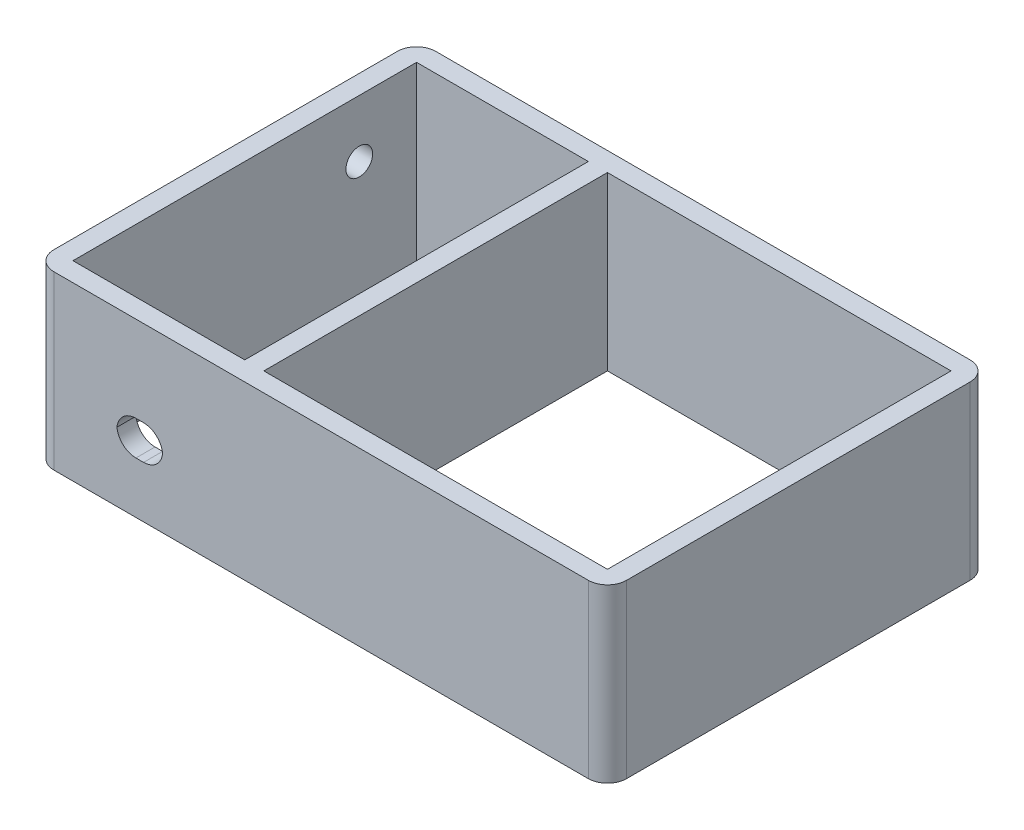
SolidWorks part; units mm, degrees
ref_plane "Front Plane" through (0, 0, 0) normal (0, 0, 1) x (1, 0, 0)
ref_plane "Top Plane" through (0, 0, 0) normal (0, 1, 0) x (1, 0, 0)
ref_plane "Right Plane" through (0, 0, 0) normal (1, 0, 0) x (0, 0, -1)
sketch "Sketch2" plane through (0, 0, 0) normal (0, 1, 0) x (1, 0, 0)
  line L0 (-70, -45) -> (-70, 45)
  line L1 (-75, -50) -> (75, -50)
  line L2 (-75, -50) -> (-75, 50)
  line L3 (-75, 50) -> (75, 50)
  line L4 (75, -50) -> (75, 50)
  line L5 (-75, -50) -> (75, 50) construction
  line L6 (-75, 50) -> (75, -50) construction
  line L7 (-70, 45) -> (70, 45)
  line L8 (70, -45) -> (70, 45)
  line L9 (-70, -45) -> (70, -45)
  point P0 (0, 0)
  dimension "D1" = 150
  dimension "D2" = 100
  dimension "D3" = 5
extrude "Boss-Extrude3" add sketch "Sketch2" along normal blind 45
fillet "Fillet1" radius 5 4 edges at (75, 22.5, -50) (-75, 22.5, -50) (-75, 22.5, 50) (75, 22.5, 50)
ref_plane "Plane1" through (0, 0, 0) normal (0, 1, 0) x (1, 0, 0)
sketch "Sketch3" plane through (0, 0, 0) normal (0, 1, 0) x (1, 0, 0)
  line L0 (-70, -45) -> (70, -45) construction
  line L1 (70, 45) -> (-20, 45) construction
  line L2 (70, 45) -> (70, -45) construction
  line L3 (70, -45) -> (-20, -45) construction
  line L4 (-20, 45) -> (-20, -45) construction
  line L6 (-20, 45) -> (-25, 45)
  line L7 (-20, 45) -> (-20, -45)
  line L8 (-20, -45) -> (-25, -45)
  line L9 (-25, 45) -> (-25, -45)
  dimension "D1" = 90
  dimension "D2" = 5
extrude "Boss-Extrude4" add sketch "Sketch3" along normal blind 45
ref_plane "Plane2" through (0, 0, 50) normal (0, 0, 1) x (1, 0, 0)
sketch "Sketch4" plane through (0, 0, 50) normal (0, 0, 1) x (1, 0, 0)
  line L0 (-70, 0) -> (70, 0) construction
  line L1 (-70, 45) -> (-25, 45) construction
  line L2 (-70, 45) -> (-70, 0) construction
  line L3 (-70, 0) -> (-25, 0) construction
  line L4 (-25, 45) -> (-25, 0) construction
  line L5 (-47.5, 45) -> (-47.5, 0) construction
  line L6 (-70, 18) -> (-25, 18) construction
  dimension "D1" = 45
  dimension "D2" = 18
sketch "Sketch5" plane through (0, 0, 50) normal (0, 0, 1) x (1, 0, 0)
  line L0 (-70, 18) -> (-25, 18) construction
  line L1 (-53.5, 13.5) -> (-41.5, 13.5)
  line L2 (-53.5, 13.5) -> (-53.5, 22.5)
  line L3 (-53.5, 22.5) -> (-41.5, 22.5)
  line L4 (-41.5, 13.5) -> (-41.5, 22.5)
  line L5 (-53.5, 13.5) -> (-41.5, 22.5) construction
  line L6 (-53.5, 22.5) -> (-41.5, 13.5) construction
  point P0 (-47.5, 18)
  dimension "D1" = 12
  dimension "D2" = 9
extrude "Cut-Extrude1" cut sketch "Sketch5" against normal blind 5 contours L3 L4 L1 L2
fillet "Fillet2" radius 5 4 edges at (-53.5, 13.5, 47.5) (-53.5, 22.5, 47.5) (-41.5, 22.5, 47.5) (-41.5, 13.5, 47.5)
ref_plane "Plane3" through (-75, 0, 0) normal (-1, 0, 0) x (0, 0, 1)
sketch "Sketch6" plane through (-75, 0, 0) normal (-1, 0, 0) x (0, 0, 1)
  line L0 (-45, 30) -> (45, 30) construction
  line L1 (-45, 45) -> (45, 45) construction
  line L2 (-45, 45) -> (-45, 0) construction
  line L3 (-45, 0) -> (45, 0) construction
  line L4 (45, 45) -> (45, 0) construction
  line L5 (-30, 45) -> (-30, 0) construction
  circle A0 centre (-30, 30) radius 3.5
  dimension "D3" = 7
  dimension "D1" = 15
  dimension "D2" = 15
extrude "Cut-Extrude2" cut sketch "Sketch6" against normal blind 5 contours A0
